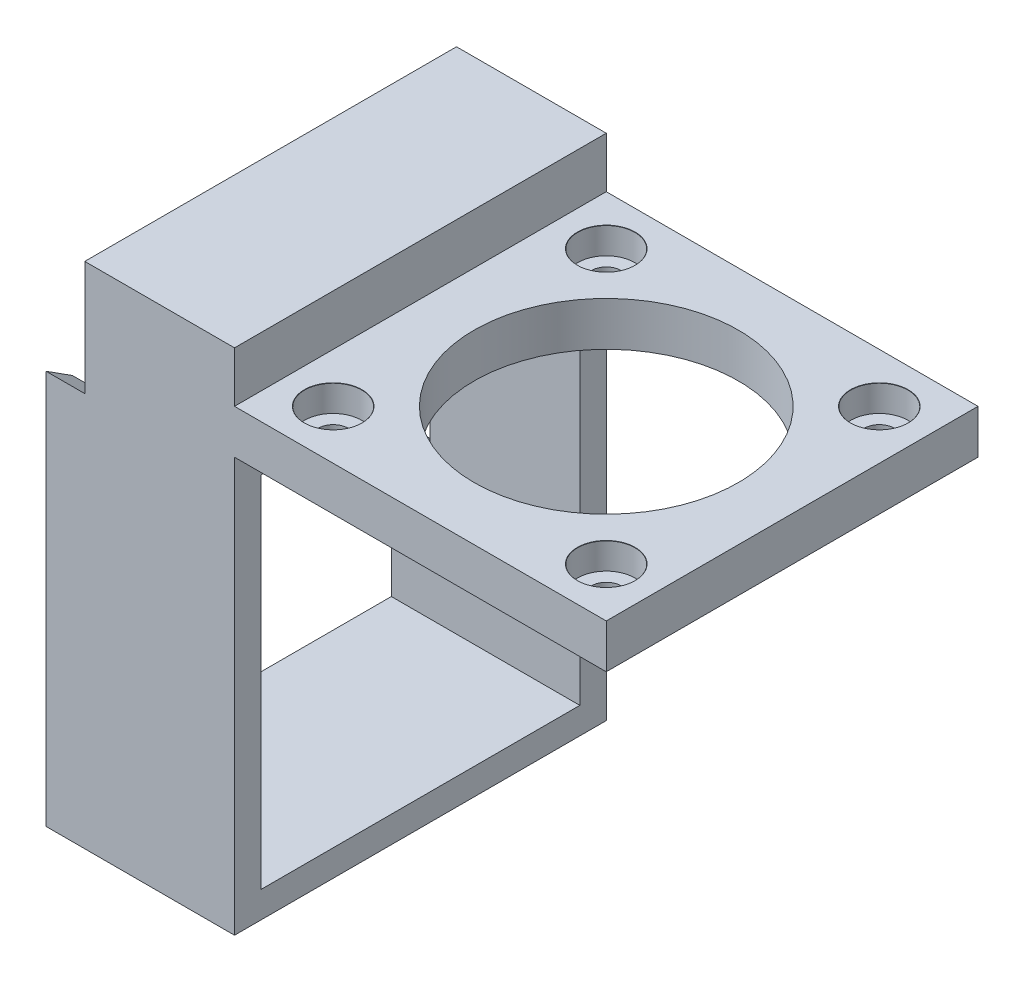
SolidWorks part; units mm, degrees
ref_plane "Front Plane" through (0, 0, 0) normal (0, 0, 1) x (1, 0, 0)
ref_plane "Top Plane" through (0, 0, 0) normal (0, 1, 0) x (1, 0, 0)
ref_plane "Right Plane" through (0, 0, 0) normal (1, 0, 0) x (0, 0, -1)
sketch "Sketch1" plane through (0, 0, 0) normal (1, 0, 0) x (0, 0, -1)
  line L0 (-41.2795, 57.75) -> (41.2795, 57.75) construction
  line L1 (-21.1, 57.75) -> (21.1, 57.75)
  line L2 (-21.1, 57.75) -> (-21.1, 0)
  line L3 (-21.1, 0) -> (21.1, 0)
  line L4 (21.1, 57.75) -> (21.1, 0)
  line L5 (21.1, 47) -> (21.1, 38.9) construction
  point P5 (-39.1842, 51.2543)
  point P6 (0, 57.75)
extrude "Boss-Extrude1" add sketch "Sketch1" along normal up to surface (17 mm away)
sketch "Sketch2" plane through (17, 0, 0) normal (1, 0, 0) x (0, 0, -1)
  line L0 (-21.1, 57.75) -> (-21.1, 0) construction
  line L1 (-21.1, 52) -> (21.1, 52)
  line L2 (-21.1, 52) -> (-21.1, 47)
  line L3 (-21.1, 47) -> (21.1, 47)
  line L4 (21.1, 52) -> (21.1, 47)
  dimension "D1" = 5
extrude "Boss-Extrude2" add sketch "Sketch2" along normal up to surface (42.2 mm away)
sketch "Sketch3" plane through (0, 52, 0) normal (0, 1, 0) x (1, 0, 0)
  circle A0 centre (53.6, -15.5) radius 1.275 construction
  circle A1 centre (53.6, 15.5) radius 1.275 construction
  circle A2 centre (53.6, -15.5) radius 1.275
  circle A3 centre (53.6, 15.5) radius 1.275
  circle A4 centre (22.6, 15.5) radius 1.275 construction
  circle A5 centre (22.6, 15.5) radius 1.275
  circle A6 centre (22.6, -15.5) radius 1.275 construction
  circle A7 centre (22.6, -15.5) radius 1.275
  point P0 (53.6, -15.5)
  point P2 (53.6, 15.5)
  point P6 (22.6, 15.5)
  point P9 (22.6, -15.5)
hole_wizard "CBORE for M3 SHCS1" positions "Sketch3" profile "Sketch4" counterbore size "M3" standard "ANSI Metric" end condition through all
sketch "Sketch4" plane through (53.6, 52, 15.5) normal (1, 0, 0) x (0, 0, 1)
  line L0 (0, 0) -> (0, 52)
  line L1 (0, 52) -> (1.7, 52)
  line L3 (1.7, 52) -> (1.7, 3)
  line L4 (3.25, 3) -> (1.7, 3)
  line L5 (3.25, 3) -> (3.25, 0.025)
  line L6 (3.25, 0.025) -> (3.275, 0)
  line L7 (3.275, 0) -> (0, 0)
  line L8 (-3.25, 0.025) -> (-3.275, 0) construction
  line L11 (0, -6.35) -> (0, 107.95) construction
  dimension "Thru Hole Dia." = 3.4
  dimension "Thru Hole Depth" = 52
  dimension "C'Bore Dia." = 6.5
  dimension "C'Bore Depth" = 3
  dimension "Near C'Sink Dia." = 6.55
  dimension "Near C'Sink Angle" = 90
sketch "Sketch5" plane through (0, 52, 0) normal (0, 1, 0) x (1, 0, 0)
  circle A0 centre (38.1, 0) radius 15
  dimension "D1" = 30
extrude "Cut-Extrude1" cut sketch "Sketch5" against normal through all
sketch "Sketch6" plane through (0, 0, 0) normal (1, 0, 0) x (0, 0, -1)
  line L0 (-21.1, 44.75) -> (21.1, 17.75)
  line L2 (21.1, 52) -> (21.1, 47) construction
  line L3 (21.1, 57.75) -> (-21.1, 57.75) construction
  line L4 (21.1, 17.75) -> (21.1, 0)
  line L5 (21.1, 0) -> (-21.1, 0)
  line L6 (-21.1, 0) -> (-21.1, 44.75)
  line L7 (-21.1, 57.75) -> (-21.1, 0) construction
  line L8 (-21.1, 0) -> (21.1, 0) construction
  point P9 (-21.1, 44.75)
  point P13 (-21.1, 0)
  point P14 (21.1, 0)
  point P17 (-21.1, 0)
  dimension "D1" = 13
  dimension "D2" = 40
extrude "Boss-Extrude3" add sketch "Sketch6" against normal blind 4.4
sketch "Sketch7" plane through (17, 0, 0) normal (1, 0, 0) x (0, 0, -1)
  line L0 (21.1, 57.75) -> (-21.1, 57.75) construction
  line L1 (-18.1, 43.75) -> (18.1, 43.75)
  line L2 (-18.1, 43.75) -> (-18.1, 3)
  line L3 (-18.1, 3) -> (18.1, 3)
  line L4 (18.1, 43.75) -> (18.1, 3)
  line L5 (21.1, 52) -> (21.1, 47) construction
  line L6 (-21.1, 47) -> (-21.1, 52) construction
  line L7 (-21.1, 0) -> (21.1, 0) construction
  dimension "D1" = 14
  dimension "D2" = 3
  dimension "D3" = 3
  dimension "D4" = 3
extrude "Cut-Extrude2" cut sketch "Sketch7" against normal through all
